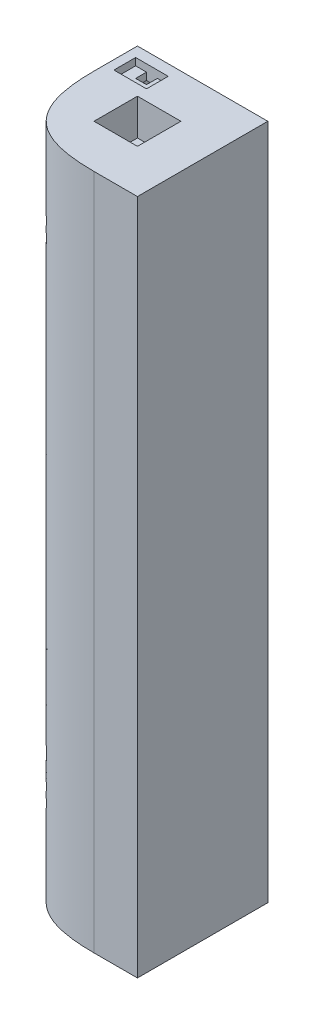
SolidWorks part; units mm, degrees
ref_plane "Front Plane" through (0, 0, 0) normal (0, 0, 1) x (1, 0, 0)
ref_plane "Top Plane" through (0, 0, 0) normal (0, 1, 0) x (1, 0, 0)
ref_plane "Right Plane" through (0, 0, 0) normal (1, 0, 0) x (0, 0, -1)
sketch "Sketch1" plane through (0, 0, 0) normal (0, 1, 0) x (1, 0, 0)
  line L1 (0, 0) -> (36, 0)
  line L2 (0, 0) -> (0, 36)
  line L3 (0, 36) -> (36, 36)
  line L4 (36, 0) -> (36, 36)
  dimension "D1" = 36
  dimension "D2" = 36
extrude "Boss-Extrude1" add sketch "Sketch1" along normal blind 186.9
fillet "Fillet1" radius 24 1 edges at (0, 93.45, 0) conic rho 0.55
sketch "Sketch2" plane through (0, 0, 0) normal (0, -1, 0) x (1, 0, 0)
  line L0 (36, -36) -> (0, -36) construction
  line L2 (36, 0) -> (36, -36) construction
  line L3 (24, 0) -> (36, 0) construction
  circle A0 centre (18, -18) radius 2
  dimension "D1" = 4
  dimension "D2" = 18
  dimension "D3" = 18
extrude "Cut-Extrude1" cut sketch "Sketch2" against normal blind 5
sketch "Sketch3" plane through (0, 0, 0) normal (0, -1, 0) x (1, 0, 0)
  line L0 (36, 0) -> (36, -36) construction
  line L1 (26, -5) -> (31, -5)
  line L2 (26, -5) -> (26, -26)
  line L3 (26, -31) -> (31, -31)
  line L4 (31, -5) -> (31, -31)
  line L5 (24, 0) -> (36, 0) construction
  line L6 (36, -36) -> (0, -36) construction
  line L7 (0, -36) -> (0, -24) construction
  line L8 (5, -31) -> (26, -31)
  line L9 (5, -31) -> (5, -26)
  line L10 (5, -26) -> (26, -26)
  line L13 (9, -9) -> (14, -9)
  line L14 (9, -9) -> (9, -14)
  line L15 (9, -14) -> (14, -14)
  line L16 (14, -9) -> (14, -14)
  dimension "D7" = 5
  dimension "D8" = 5
  dimension "D9" = 12
  dimension "D1" = 5
  dimension "D2" = 5
  dimension "D3" = 5
  dimension "D4" = 5
  dimension "D5" = 5
  dimension "D6" = 5
  dimension "D10" = 12
  dimension "D11" = 9
  dimension "D12" = 9
extrude "Boss-Extrude2" add sketch "Sketch3" along normal blind 4
sketch "Sketch4" plane through (0, 0, -36) normal (0, 0, -1) x (-1, 0, 0)
  line L0 (0, 186.9) -> (0, 0) construction
  line L1 (-10, 182.9) -> (-4, 182.9)
  line L2 (-10, 182.9) -> (-10, 178.9)
  line L3 (-10, 178.9) -> (-4, 178.9)
  line L4 (-4, 182.9) -> (-4, 178.9)
  line L5 (-36, 186.9) -> (0, 186.9) construction
  line L6 (-36, 186.9) -> (-36, 0) construction
  line L7 (-32, 182.9) -> (-26, 182.9)
  line L8 (-32, 182.9) -> (-32, 178.9)
  line L9 (-32, 178.9) -> (-26, 178.9)
  line L10 (-26, 182.9) -> (-26, 178.9)
  line L12 (-10, 162.9) -> (-4, 162.9)
  line L13 (-10, 162.9) -> (-10, 158.9)
  line L14 (-10, 158.9) -> (-4, 158.9)
  line L15 (-4, 162.9) -> (-4, 158.9)
  dimension "D1" = 4
  dimension "D2" = 4
  dimension "D3" = 4
  dimension "D4" = 6
  dimension "D5" = 6
  dimension "D6" = 4
  dimension "D7" = 4
  dimension "D8" = 4
  dimension "D9" = 16
  dimension "D10" = 4
extrude "Cut-Extrude2" cut sketch "Sketch4" against normal blind 9
sketch "Sketch5" plane through (0, 186.9, 0) normal (0, 1, 0) x (1, 0, 0)
  line L0 (0, 36) -> (0, 24) construction
  line L1 (5.5, 33) -> (8.5, 33)
  line L2 (5.5, 33) -> (5.5, 30)
  line L3 (5.5, 30) -> (8.5, 30)
  line L4 (8.5, 33) -> (8.5, 30)
  line L5 (36, 36) -> (0, 36) construction
  line L6 (24, 0) -> (36, 0) construction
  line L7 (12, 12) -> (24, 12)
  line L8 (12, 12) -> (12, 24)
  line L9 (12, 24) -> (24, 24)
  line L10 (24, 12) -> (24, 24)
  dimension "D1" = 3
  dimension "D2" = 3
  dimension "D3" = 5.5
  dimension "D4" = 3
  dimension "D5" = 12
  dimension "D6" = 12
  dimension "D7" = 12
  dimension "D8" = 12
extrude "Cut-Extrude3" cut sketch "Sketch5" against normal blind 10
sketch "Sketch6" plane through (0, 186.9, 0) normal (0, 1, 0) x (1, 0, 0)
  line L0 (5.5, 33) -> (5.5, 30) construction
  line L1 (2.5, 33) -> (11.5, 33)
  line L2 (2.5, 33) -> (2.5, 27)
  line L3 (2.5, 27) -> (11.5, 27)
  line L4 (11.5, 33) -> (11.5, 27)
  line L5 (8.5, 30) -> (8.5, 33) construction
  line L6 (8.5, 33) -> (5.5, 33) construction
  line L7 (5.5, 30) -> (8.5, 30) construction
  dimension "D1" = 3
  dimension "D2" = 3
  dimension "D3" = 0
  dimension "D4" = 3
extrude "Cut-Extrude4" cut sketch "Sketch6" against normal blind 2
